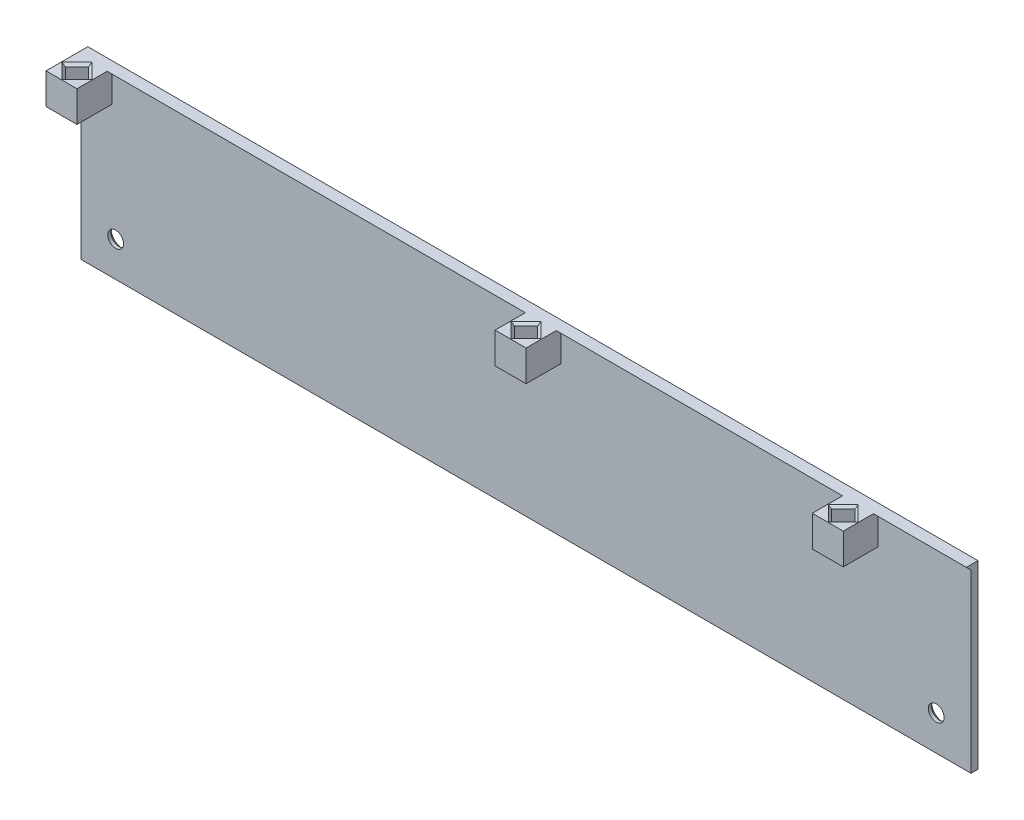
SolidWorks part; units mm, degrees
ref_plane "Front Plane" through (0, 0, 0) normal (0, 0, 1) x (1, 0, 0)
ref_plane "Top Plane" through (0, 0, 0) normal (0, 1, 0) x (1, 0, 0)
ref_plane "Right Plane" through (0, 0, 0) normal (1, 0, 0) x (0, 0, -1)
sketch "Sketch1" plane through (0, 0, 0) normal (0, 0, 1) x (1, 0, 0)
  line L1 (0, 0) -> (243.332, 0)
  line L2 (0, 0) -> (0, 49.395)
  line L3 (0, 49.395) -> (243.332, 49.395)
  line L4 (243.332, 0) -> (243.332, 49.395)
  dimension "D1" = 49.395
  dimension "D2" = 243.332
extrude "Boss-Extrude1" add sketch "Sketch1" along normal blind 1.905
sketch "Sketch2" plane through (0, 0, 1.905) normal (0, 0, 1) x (1, 0, 0)
  line L0 (243.332, 49.395) -> (0, 49.395) construction
  line L1 (0, 49.395) -> (8.4667, 49.395)
  line L2 (0, 49.395) -> (0, 40.9283)
  line L3 (0, 40.9283) -> (8.4667, 40.9283)
  line L4 (8.4667, 49.395) -> (8.4667, 40.9283)
  line L5 (122.7667, 49.395) -> (131.2333, 49.395)
  line L6 (122.7667, 49.395) -> (122.7667, 40.9283)
  line L7 (122.7667, 40.9283) -> (131.2333, 40.9283)
  line L8 (131.2333, 49.395) -> (131.2333, 40.9283)
  line L9 (243.332, 0) -> (243.332, 49.395) construction
  line L10 (209.4653, 49.395) -> (217.932, 49.395)
  line L11 (209.4653, 49.395) -> (209.4653, 40.9283)
  line L12 (209.4653, 40.9283) -> (217.932, 40.9283)
  line L13 (217.932, 49.395) -> (217.932, 40.9283)
  dimension "D1" = 114.3
  dimension "D2" = 25.4
  dimension "D4" = 8.4667
extrude "Boss-Extrude2" add sketch "Sketch2" along normal blind 9.525
sketch "Sketch3" plane through (0, 49.395, 0) normal (0, 1, 0) x (1, 0, 0)
  line L0 (1.0583, -7.1967) -> (4.2333, -4.0217)
  line L1 (1.0583, -7.1967) -> (4.2333, -10.3717)
  line L2 (4.2333, -4.0217) -> (7.4083, -7.1967)
  line L3 (4.2333, -10.3717) -> (7.4083, -7.1967)
  line L4 (1.0583, -7.1967) -> (7.4083, -7.1967) construction
  line L5 (4.2333, -4.0217) -> (4.2333, -10.3717) construction
  line L6 (123.825, -7.1967) -> (127, -4.0217)
  line L7 (123.825, -7.1967) -> (127, -10.3717)
  line L8 (127, -4.0217) -> (130.175, -7.1967)
  line L9 (127, -10.3717) -> (130.175, -7.1967)
  line L10 (123.825, -7.1967) -> (130.175, -7.1967) construction
  line L11 (127, -4.0217) -> (127, -10.3717) construction
  line L12 (210.5237, -7.1967) -> (213.6987, -4.0217)
  line L13 (210.5237, -7.1967) -> (213.6987, -10.3717)
  line L14 (213.6987, -4.0217) -> (216.8737, -7.1967)
  line L15 (213.6987, -10.3717) -> (216.8737, -7.1967)
  line L16 (210.5237, -7.1967) -> (216.8737, -7.1967) construction
  line L17 (213.6987, -4.0217) -> (213.6987, -10.3717) construction
  line L18 (8.4667, -11.43) -> (0, -11.43) construction
  line L19 (131.2333, -11.43) -> (122.7667, -11.43) construction
  line L20 (217.932, -11.43) -> (209.4653, -11.43) construction
  point P1 (4.2333, -7.1967)
  point P2 (127, -7.1967)
  point P3 (213.6987, -7.1967)
  point P13 (4.2333, -11.43)
  point P20 (127, -11.43)
  point P23 (213.6987, -11.43)
  dimension "D1" = 6.35
  dimension "D2" = 4.2333
extrude "Cut-Extrude1" cut sketch "Sketch3" against normal blind 6.35
chamfer "Chamfer1" distance 0.635 angle 45 24 edges at (212.1112, 43.045, 5.6092) (215.2862, 43.045, 5.6092) (215.2862, 43.045, 8.7842) (212.1112, 43.045, 8.7842) (2.6458, 43.045, 5.6092) (5.8208, 43.045, 5.6092) (5.8208, 43.045, 8.7842) (2.6458, 43.045, 8.7842) (125.4125, 43.045, 5.6092) (128.5875, 43.045, 5.6092) (128.5875, 43.045, 8.7842) (125.4125, 43.045, 8.7842) (212.1112, 49.395, 5.6092) (212.1112, 49.395, 8.7842) (215.2862, 49.395, 5.6092) (215.2862, 49.395, 8.7842) (2.6458, 49.395, 5.6092) (2.6458, 49.395, 8.7842) (5.8208, 49.395, 5.6092) (5.8208, 49.395, 8.7842) (128.5875, 49.395, 8.7842) (128.5875, 49.395, 5.6092) (125.4125, 49.395, 5.6092) (125.4125, 49.395, 8.7842)
sketch "Sketch4" plane through (243.332, 0, 0) normal (1, 0, 0) x (0, 0, -1)
  line L0 (-3.175, 49.395) -> (-1.905, 49.395)
  line L1 (-11.43, 49.395) -> (-1.905, 49.395) construction
  line L2 (-1.905, 0) -> (-1.905, 49.395) construction
  line L3 (-1.905, 49.395) -> (-1.905, 48.125)
  line L4 (-1.905, 48.125) -> (-3.175, 49.395)
  dimension "D1" = 1.27
extrude "Boss-Extrude3" add sketch "Sketch4" against normal up to surface (243.332 mm away) up to face at (0, 30.1078, 4.445)
sketch "Sketch5" plane through (0, 0, 0) normal (0, 0, -1) x (-1, 0, 0)
  line L0 (-243.332, 9.525) -> (-233.807, 9.525) construction
  line L1 (-243.332, 0) -> (-243.332, 49.395) construction
  line L2 (-233.807, 9.525) -> (-233.807, 0) construction
  line L3 (0, 0) -> (-243.332, 0) construction
  line L4 (0, 9.525) -> (-9.525, 9.525) construction
  line L5 (0, 49.395) -> (0, 0) construction
  line L6 (-9.525, 9.525) -> (-9.525, 0) construction
  point P13 (-9.525, 9.525)
  point P14 (-233.807, 9.525)
  dimension "D1" = 9.525
hole_wizard "#6 Clearance Hole1" positions "Sketch5" profile "Sketch6" hole size "#6" standard "ANSI Inch" end condition through all
sketch "Sketch6" plane through (233.807, 9.525, 0) normal (1, 0, 0) x (0, 1, 0)
  line L0 (0, 0) -> (0, 11.43)
  line L1 (0, 11.43) -> (2.1526, 11.43)
  line L2 (2.1526, 11.43) -> (2.1526, 1.0223)
  line L3 (2.1526, 1.0223) -> (3.175, 0)
  line L5 (3.175, 0) -> (0, 0)
  line L6 (-2.1526, 1.0223) -> (-3.175, 0) construction
  line L11 (0, -6.35) -> (0, 107.95) construction
  dimension "Thru Hole Dia." = 4.3053
  dimension "Thru Hole Depth" = 11.43
  dimension "Near C'Sink Dia." = 6.35
  dimension "Near C'Sink Angle" = 90
